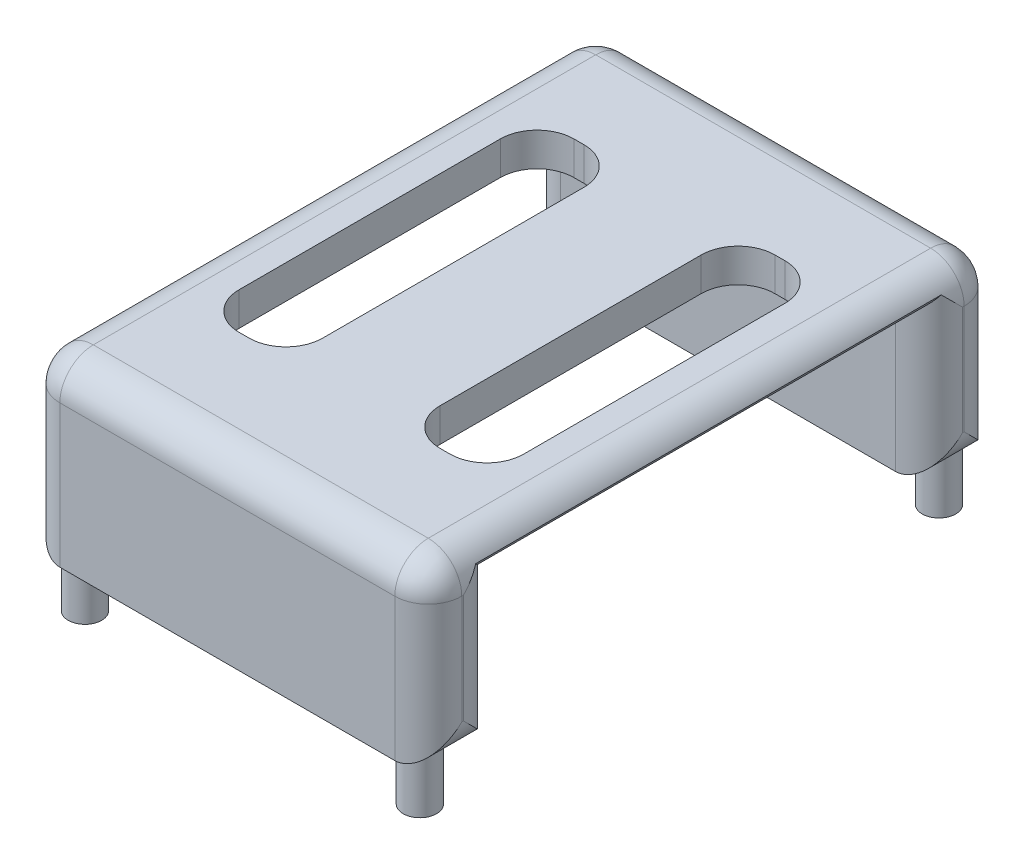
SolidWorks part; units mm, degrees
material "自定义塑料"
ref_plane "Front" through (0, 0, 0) normal (0, 0, 1) x (1, 0, 0)
ref_plane "Top" through (0, 0, 0) normal (0, 1, 0) x (1, 0, 0)
ref_plane "Right" through (0, 0, 0) normal (1, 0, 0) x (0, 0, -1)
sketch "草图1" plane through (0, 0, 0) normal (0, 1, 0) x (1, 0, 0)
  line L1 (-23, 12.9) -> (23, 12.9)
  line L2 (-23, 12.9) -> (-23, -12.9)
  line L3 (-23, -12.9) -> (23, -12.9)
  line L4 (23, 12.9) -> (23, -12.9)
  line L5 (-23, 12.9) -> (23, -12.9) construction
  line L6 (-23, -12.9) -> (23, 12.9) construction
  line L7 (-10, 15.5) -> (10, 15.5)
  line L8 (-10, 15.5) -> (-10, -15.5)
  line L9 (-10, -15.5) -> (10, -15.5)
  line L10 (10, 15.5) -> (10, -15.5)
  line L11 (-10, 15.5) -> (10, -15.5) construction
  line L12 (-10, -15.5) -> (10, 15.5) construction
  line L13 (-12, 17) -> (12, 17)
  line L14 (-12, 17) -> (-12, -17)
  line L15 (-12, -17) -> (12, -17)
  line L16 (12, 17) -> (12, -17)
  line L17 (-12, 17) -> (12, -17) construction
  line L18 (-12, -17) -> (12, 17) construction
  point P0 (0, 0)
  point P5 (0, 0)
  point P11 (0, 0)
  dimension "D1" = 25.8
extrude "凸台-拉伸1" add sketch "草图1" along normal blind 8.5 contours L16 L3 L10 L9 L8 L14 L15 | L10 L3 L8 L9 | L10 L7 L8 L1 | L16 L13 L14 L1 L8 L7 L10
sketch "草图2" plane through (0, 8.5, 0) normal (0, 1, 0) x (1, 0, 0)
  line L1 (12, -17) -> (-12, -17)
  line L2 (12, -17) -> (12, 17)
  line L3 (12, 17) -> (-12, 17)
  line L4 (-12, -17) -> (-12, 17)
extrude "凸台-拉伸2" add sketch "草图2" along normal blind 2
fillet "圆角1" radius 2 2 edges at (0, 10.5, -17) (0, 10.5, 17)
sketch "草图3" plane through (0, 0, 0) normal (0, -1, 0) x (-1, 0, 0)
  line L1 (-10, -15.5) -> (10, -15.5)
  line L2 (-10, -15.5) -> (-10, 15.5)
  line L3 (-10, 15.5) -> (10, 15.5)
  line L4 (10, -15.5) -> (10, 15.5)
  line L5 (-10, -15.5) -> (10, 15.5) construction
  line L6 (-10, 15.5) -> (10, -15.5) construction
  circle A0 centre (-10, -15.5) radius 1
  circle A1 centre (10, -15.5) radius 1
  circle A2 centre (-10, 15.5) radius 1
  circle A3 centre (10, 15.5) radius 1
  point P0 (0, 0)
extrude "凸台-拉伸3" add sketch "草图3" along normal blind 3 contours A0 | A1 | A2 | A3
fillet "圆角2" radius 2 20 edges at (12, 0, -14.95) (12, 4.25, -12.9) (12, 8.5, 0) (12, 4.25, 12.9) (12, 0, 14.95) (12, 4.25, 17) (12, 9.9142, 16.4142) (12, 10.5, 0) (12, 9.9142, -16.4142) (12, 4.25, -17) (-12, 9.9142, 16.4142) (-12, 4.25, 17) (-12, 0, 14.95) (-12, 4.25, 12.9) (-12, 8.5, 0) (-12, 4.25, -12.9) (-12, 0, -14.95) (-12, 4.25, -17) (-12, 9.9142, -16.4142) (-12, 10.5, 0)
sketch "草图4" plane through (0, 10.5, 0) normal (0, 1, 0) x (1, 0, 0)
  line L0 (-6, 0) -> (6, 0)
  line L1 (6, 0) -> (6, 10)
  line L2 (5.7, 10) -> (6.3, 10)
  line L3 (-18, 0) -> (-6, 0)
  line L4 (3.5, 10) -> (8.5, 10)
  line L5 (3.5, 7.8) -> (3.5, -7.8)
  line L6 (5.7, -10) -> (6.3, -10)
  line L7 (8.5, 7.8) -> (8.5, -7.8)
  line L8 (-6, 0) -> (-6, 10)
  line L9 (-6.3, 10) -> (-5.7, 10)
  line L10 (-8.5, 10) -> (-3.5, 10)
  line L11 (-8.5, 7.8) -> (-8.5, -7.8)
  line L12 (-6.3, -10) -> (-5.7, -10)
  line L13 (-3.5, 7.8) -> (-3.5, -7.8)
  arc A0 (6.3, -10) -> (8.5, -7.8) centre (6.3, -7.8) ccw
  arc A1 (5.7, -10) -> (3.5, -7.8) centre (5.7, -7.8) cw
  arc A2 (6.3, 10) -> (8.5, 7.8) centre (6.3, 7.8) cw
  arc A3 (3.5, 7.8) -> (5.7, 10) centre (5.7, 7.8) cw
  arc A4 (-5.7, -10) -> (-3.5, -7.8) centre (-5.7, -7.8) ccw
  arc A5 (-6.3, -10) -> (-8.5, -7.8) centre (-6.3, -7.8) cw
  arc A6 (-5.7, 10) -> (-3.5, 7.8) centre (-5.7, 7.8) cw
  arc A7 (-8.5, 7.8) -> (-6.3, 10) centre (-6.3, 7.8) cw
  point P4 (0, 0)
  point P9 (6, 10)
  point P20 (0, 0)
  point P28 (-6, 10)
  dimension "D1" = 2.2
  dimension "D2" = 2
extrude "切除-拉伸1" cut sketch "草图4" against normal blind 3 contours L11 A5 L12 A4 L13 A6 L9 A7 | L5 A1 L6 A0 L7 A2 L2 A3
